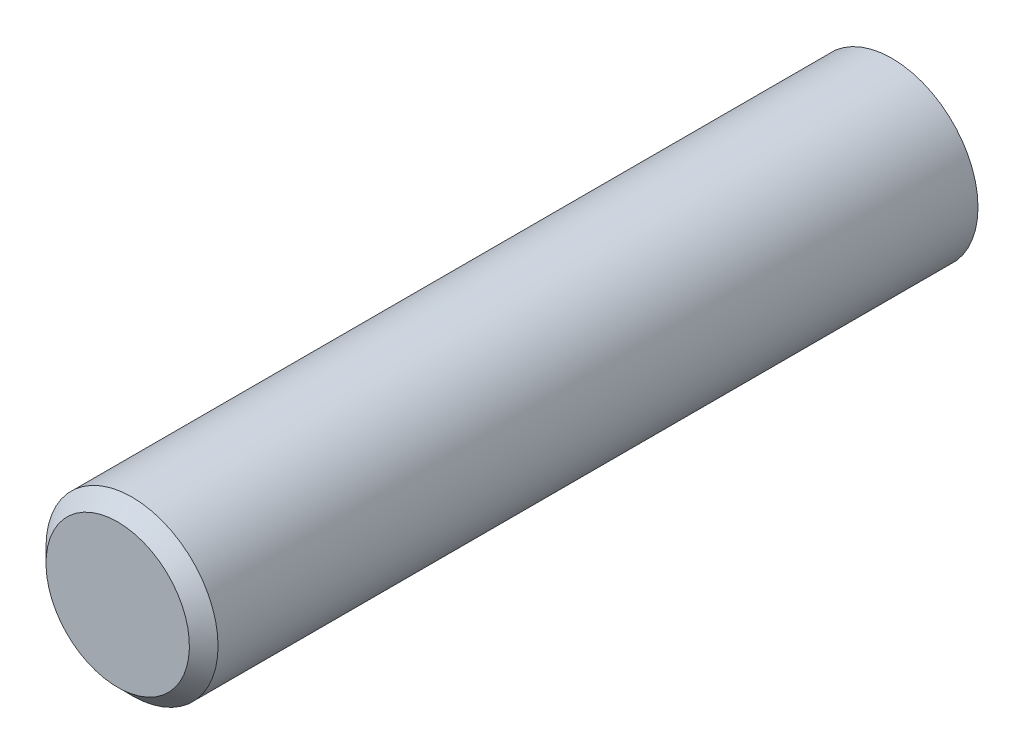
SolidWorks part; units mm, degrees
ref_plane "Ebene vorne" through (0, 0, 0) normal (0, 0, 1) x (1, 0, 0)
ref_plane "Ebene oben" through (0, 0, 0) normal (0, 1, 0) x (1, 0, 0)
ref_plane "Ebene rechts" through (0, 0, 0) normal (1, 0, 0) x (0, 0, -1)
ref_plane "Ebene1" through (85, 0, 0) normal (1, 0, 0) x (0, 0, -1)
sketch "Skizze1" plane through (85, 0, 0) normal (1, 0, 0) x (0, 0, -1)
  line L1 (-2, 3) -> (-2, 0) construction
  line L2 (2, 3) -> (-22, 3) construction
  line L3 (-22, 0) -> (0, 0) construction
  line L5 (-2, 3) -> (-2, 0)
  line L6 (-2, 3) -> (-22, 3)
  line L7 (-22, 0) -> (-2, 0)
  line L8 (-29, 0) -> (-22, 0) construction
  line L9 (-29, 3) -> (-29, 0) construction
  line L10 (-22, 3) -> (-29, 3) construction
  line L11 (-29, 0) -> (-22, 0)
  line L12 (-29, 3) -> (-29, 0)
  line L13 (-22, 3) -> (-29, 3)
revolve "Rotation1" add sketch "Skizze1" angle 360 about L7
sketch "Skizze4" plane through (0, 0, 2) normal (0, 0, -1) x (-1, 0, 0)
  point P0 (-85, 0)
hole_wizard "Ø3.1 (3.175) Durchmesser Bohrung1" positions "Skizze4" profile "Skizze5" hole size "Ø3.1" standard "DIN"
sketch "Skizze5" plane through (85, 0, 2) normal (1, 0, 0) x (0, 1, 0)
  line L0 (0, 0) -> (0, 10.9539)
  line L1 (0, 10.9539) -> (1.5875, 10)
  line L2 (1.5875, 10) -> (1.5875, 0)
  line L5 (1.5875, 0) -> (0, 0)
  line L10 (0, 10.9539) -> (-1.5875, 10) construction
  line L11 (0, -6.35) -> (0, 107.95) construction
  dimension "Bohrerdurchmesser" = 3.175
  dimension "Bohrungstiefe" = 10
  dimension "Spitzenwinkel" = 118
chamfer "Fase1" distance 0.5 angle 45 1 edges at (85, -3, 29)
